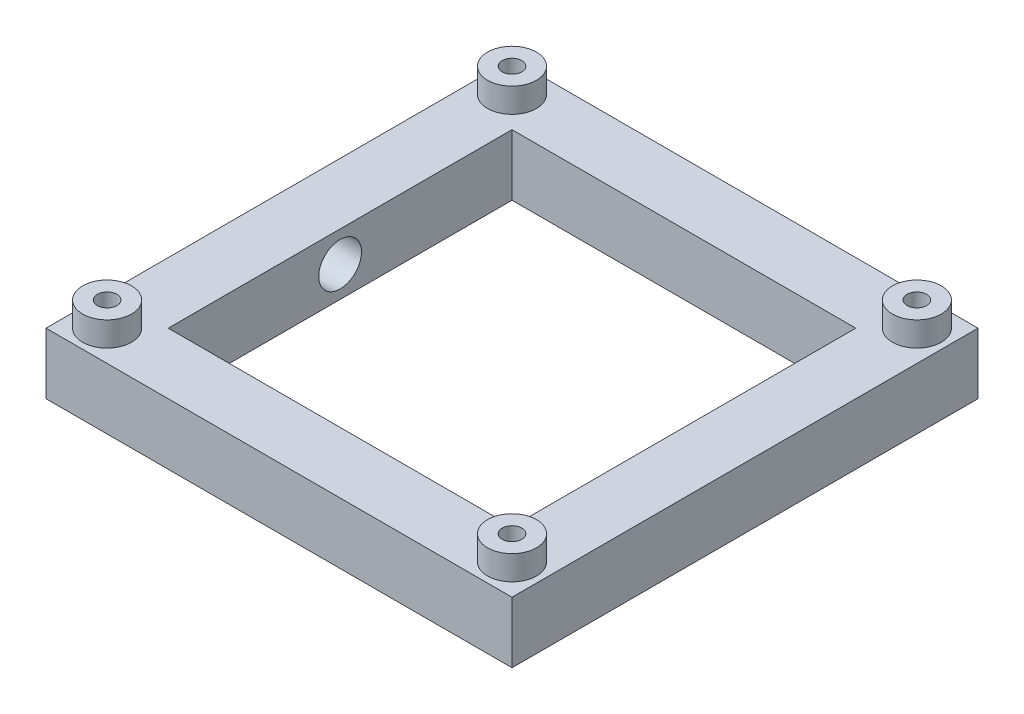
SolidWorks part; units mm, degrees
ref_plane "Front Plane" through (0, 0, 0) normal (0, 0, 1) x (1, 0, 0)
ref_plane "Top Plane" through (0, 0, 0) normal (0, 1, 0) x (1, 0, 0)
ref_plane "Right Plane" through (0, 0, 0) normal (1, 0, 0) x (0, 0, -1)
sketch "Sketch1" plane through (0, 0, 0) normal (0, 1, 0) x (1, 0, 0)
  line L1 (0, 0) -> (56.25, 0)
  line L2 (0, 0) -> (0, -56.25)
  line L3 (0, -56.25) -> (56.25, -56.25)
  line L4 (56.25, 0) -> (56.25, -56.25)
  line L5 (-10, 10) -> (66.25, 10)
  line L6 (-10, 10) -> (-10, -66.25)
  line L7 (-10, -66.25) -> (66.25, -66.25)
  line L8 (66.25, 10) -> (66.25, -66.25)
  circle A0 centre (-5, 5) radius 1.6
  circle A1 centre (61.25, 5) radius 1.6
  circle A2 centre (61.25, -61.25) radius 1.6
  circle A3 centre (-5, -61.25) radius 1.6
  circle A4 centre (61.25, 5) radius 4
  circle A5 centre (61.25, -61.25) radius 4
  circle A6 centre (-5, -61.25) radius 4
  circle A7 centre (-5, 5) radius 4
  dimension "D15" = 3.2
  dimension "D19" = 8
  dimension "D1" = 56.25
  dimension "D2" = 56.25
  dimension "D3" = 10
  dimension "D4" = 10
  dimension "D5" = 10
  dimension "D6" = 10
  dimension "D7" = 5
  dimension "D8" = 5
  dimension "D9" = 5
  dimension "D10" = 5
  dimension "D11" = 5
  dimension "D12" = 5
  dimension "D13" = 5
  dimension "D14" = 5
  dimension "D16" = 66.25
  dimension "D17" = 66.25
  dimension "D18" = 76.25
extrude "Boss-Extrude1" add sketch "Sketch1" along normal blind 10 contours L8 L5 L6 L7 A7 A6 A5 A4 L1 L4 L3 L2 | A4 A1 | A5 A2 | A6 A3 | A7 A0 region at (28.125, 0, -8.9217) region at (57.3631, 0, -5) region at (57.3631, 0, 61.25) region at (-8.8869, 0, 61.25) region at (-8.8869, 0, -5)
sketch "Sketch2" plane through (0, 0, 0) normal (1, 0, 0) x (0, 0, -1)
  line L0 (-66.25, 10) -> (-66.25, 0) construction
  line L3 (10, 10) -> (-66.25, 10) construction
  circle A0 centre (-28.125, 5) radius 3.5
  dimension "D1" = 7
  dimension "D2" = 38.125
  dimension "D3" = 5
extrude "Cut-Extrude1" cut sketch "Sketch2" against normal up to surface (10 mm away) up to face at (-10, 5, 28.125)
extrude "Boss-Extrude2" add sketch "Sketch1<3>" along normal blind 4 from surface contours A7 A0 | A6 A3 | A5 A2 | A4 A1 region at (57.3631, 0, -5) region at (57.3631, 0, 61.25) region at (-8.8869, 0, 61.25) region at (-8.8869, 0, -5) starting at face at (28.125, 10, 28.125)
sketch "Sketch1<3>" plane through (0, 0, 0) normal (0, 1, 0) x (1, 0, 0) same geometry as "Sketch1"
equation "\"D6@Sketch1\"=\"D5@Sketch1\""
equation "\"D5@Sketch1\"=\"D4@Sketch1\""
equation "\"D4@Sketch1\"=\"D3@Sketch1\""
equation "\"D8@Sketch1\"=\"D7@Sketch1\""
equation "\"D9@Sketch1\"=\"D7@Sketch1\""
equation "\"D10@Sketch1\"=\"D7@Sketch1\""
equation "\"D11@Sketch1\"=\"D9@Sketch1\""
equation "\"D12@Sketch1\"=\"D9@Sketch1\""
equation "\"D13@Sketch1\"=\"D12@Sketch1\""
equation "\"D14@Sketch1\"=\"D12@Sketch1\""
equation "\"D1@Sketch1\"=\"D2@Sketch1\""
